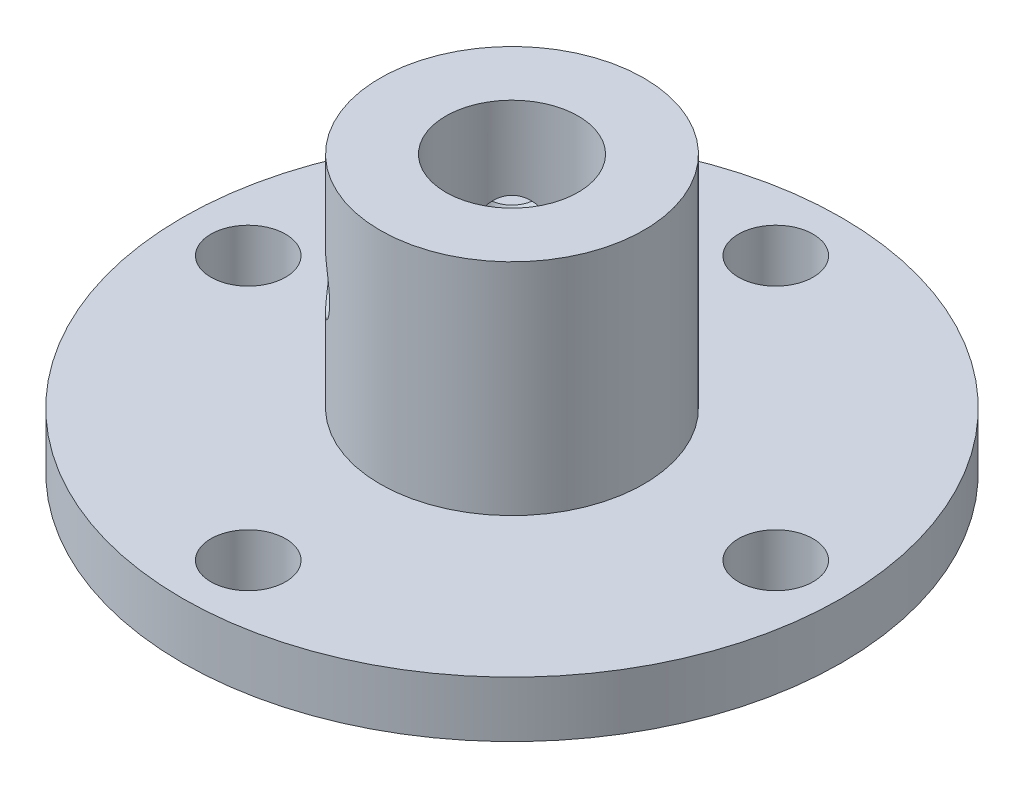
SolidWorks part; units mm, degrees
ref_plane "Front Plane" through (0, 0, 0) normal (0, 0, 1) x (1, 0, 0)
ref_plane "Top Plane" through (0, 0, 0) normal (0, 1, 0) x (1, 0, 0)
ref_plane "Right Plane" through (0, 0, 0) normal (1, 0, 0) x (0, 0, -1)
sketch "Sketch1" plane through (0, 0, 0) normal (0, 1, 0) x (1, 0, 0)
  line L0 (0, 12) -> (0, -12) construction
  line L1 (-12, 0) -> (12, 0) construction
  circle A0 centre (0, 0) radius 15
  circle A1 centre (0, 0) radius 6
  circle A2 centre (0, 0) radius 3.01
  circle A3 centre (0, 0) radius 12 construction
  dimension "D1" = 30
  dimension "D2" = 12
  dimension "D3" = 24
  dimension "D4" = 6.02
extrude "Boss-Extrude4" add sketch "Sketch1" against normal blind 2.54 contours A0 A1 | A1 A2 region at (-14.5757, 0, 0) region at (-5.8303, 0, 0)
extrude "Boss-Extrude5" add sketch "Sketch1<8>" along normal blind 10 contours A2 | A1
sketch "Sketch1<8>" plane through (0, 0, 0) normal (0, 1, 0) x (1, 0, 0) same geometry as "Sketch1"
sketch "Sketch4" plane through (0, 0, 0) normal (0, 1, 0) x (1, 0, 0)
  point P0 (0, 12)
  point P3 (12, 0)
  point P6 (-12, 0)
  point P9 (0, -12)
hole_wizard "M3 Clearance Hole1" positions "Sketch4" profile "Sketch3" hole size "M3" standard "ANSI Metric" end condition up to next
sketch "Sketch3" plane through (0, 0, -12) normal (1, 0, 0) x (0, 0, 1)
  line L0 (0, 0) -> (0, 2.54)
  line L1 (0, 2.54) -> (1.7, 2.54)
  line L2 (1.7, 2.54) -> (1.7, 0)
  line L5 (1.7, 0) -> (0, 0)
  line L11 (0, -6.35) -> (0, 107.95) construction
  dimension "Thru Hole Dia." = 3.4
  dimension "Thru Hole Depth" = 2.54
ref_plane "Plane2" through (-4.2426, 0, -4.2426) normal (-0.7071, 0, -0.7071) x (0, -1, 0)
sketch "Sketch9" plane through (-4.2426, 0, -4.2426) normal (-0.7071, 0, -0.7071) x (0, -1, 0)
  line L0 (-10, 0) -> (0, 0) construction
  line L1 (-10, 6) -> (-10, -6) construction
  line L2 (-5, -6) -> (-5, 6) construction
  line L3 (-10, -6) -> (0, -6) construction
  line L4 (0, 6) -> (-10, 6) construction
sketch "Sketch12" plane through (-4.2426, 0, -4.2426) normal (-0.7071, 0, -0.7071) x (0, -1, 0)
  line L0 (-10, 0) -> (0, 0) construction
  point P0 (-5, 0)
hole_wizard "Tap Drill for M3x0.5 Tap1" positions "Sketch12" profile "Sketch11" hole size "M3x0.5" standard "ANSI Metric" end condition up to next
sketch "Sketch11" plane through (-4.2426, 5, -4.2426) normal (0, 1, 0) x (-0.7071, 0, 0.7071)
  line L0 (0, 0) -> (0, 2.99)
  line L1 (0, 2.99) -> (1.25, 2.99)
  line L2 (1.25, 2.99) -> (1.25, 0)
  line L5 (1.25, 0) -> (0, 0)
  line L11 (0, -6.35) -> (0, 107.95) construction
  dimension "Thru Hole Dia." = 2.5
  dimension "Thru Hole Depth" = 2.99
ref_plane "Plane3" through (-4.2426, 0, 4.2426) normal (-0.7071, 0, 0.7071) x (0, -1, 0)
sketch "Sketch15" plane through (-4.2426, 0, 4.2426) normal (-0.7071, 0, 0.7071) x (0, -1, 0)
  line L0 (-10, 0) -> (0, 0) construction
  line L1 (-10, 6) -> (-10, -6) construction
  line L2 (-5, 6) -> (-5, -6) construction
  line L3 (0, 6) -> (-10, 6) construction
  line L4 (-55, -6) -> (55, -6) construction
sketch "Sketch18" plane through (-4.2426, 0, 4.2426) normal (-0.7071, 0, 0.7071) x (0, -1, 0)
  line L0 (-10, 0) -> (0, 0) construction
  point P0 (-5, 0)
hole_wizard "Tap Drill for M3x0.5 Tap2" positions "Sketch18" profile "Sketch17" hole size "M3x0.5" standard "ANSI Metric" end condition up to next
sketch "Sketch17" plane through (-4.2426, 5, 4.2426) normal (0, 1, 0) x (0.7071, 0, 0.7071)
  line L0 (0, 0) -> (0, 2.99)
  line L1 (0, 2.99) -> (1.25, 2.99)
  line L2 (1.25, 2.99) -> (1.25, 0)
  line L5 (1.25, 0) -> (0, 0)
  line L11 (0, -6.35) -> (0, 107.95) construction
  dimension "Thru Hole Dia." = 2.5
  dimension "Thru Hole Depth" = 2.99
